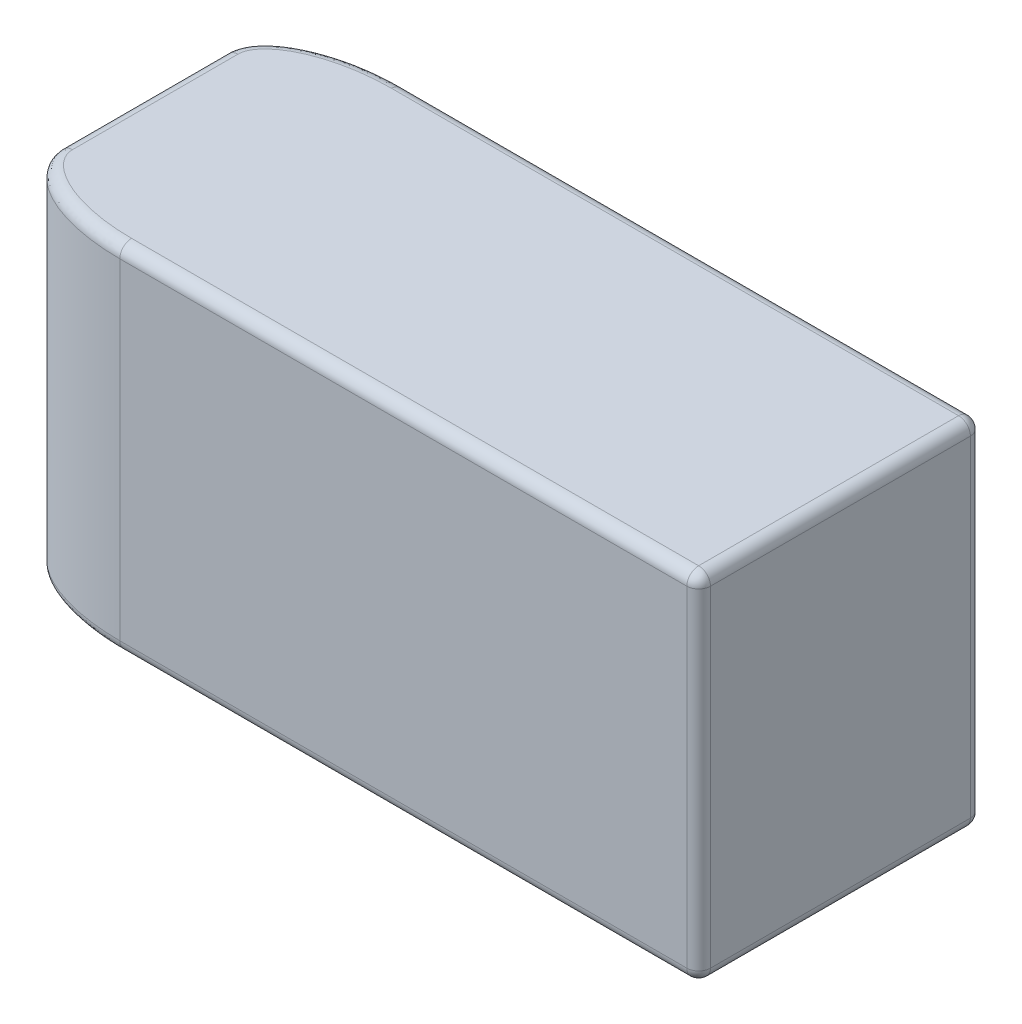
SolidWorks part; units mm, degrees
material "Rubber"
ref_plane "Front Plane" through (0, 0, 0) normal (0, 0, 1) x (1, 0, 0)
ref_plane "Top Plane" through (0, 0, 0) normal (0, 1, 0) x (1, 0, 0)
ref_plane "Right Plane" through (0, 0, 0) normal (1, 0, 0) x (0, 0, -1)
sketch "Sketch1" plane through (0, 0, 0) normal (0, 1, 0) x (1, 0, 0)
  line L1 (-29.5, -12) -> (29.5, -12)
  line L2 (-29.5, -12) -> (-29.5, 12)
  line L3 (-29.5, 12) -> (29.5, 12)
  line L4 (29.5, -12) -> (29.5, 12)
  line L5 (-29.5, -12) -> (29.5, 12) construction
  line L6 (-29.5, 12) -> (29.5, -12) construction
  point P0 (0, 0)
  dimension "D1" = 24
  dimension "D2" = 59
extrude "Boss-Extrude1" add sketch "Sketch1" along normal mid plane 30
fillet "Fillet1" radius 1 2 edges at (29.5, 0, -12) (29.5, 0, 12)
fillet "Fillet2" radius 5 2 edges at (-29.5, 0, -12) (-29.5, 0, 12) second distance 10 first distance on face at (-29.5, 0, 0)
fillet "Fillet3" radius 1 16 edges at (29.2071, -15, -11.7071) (29.5, -15, 0) (29.2071, -15, 11.7071) (29.2071, 15, -11.7071) (29.5, 15, 0) (29.2071, 15, 11.7071)
